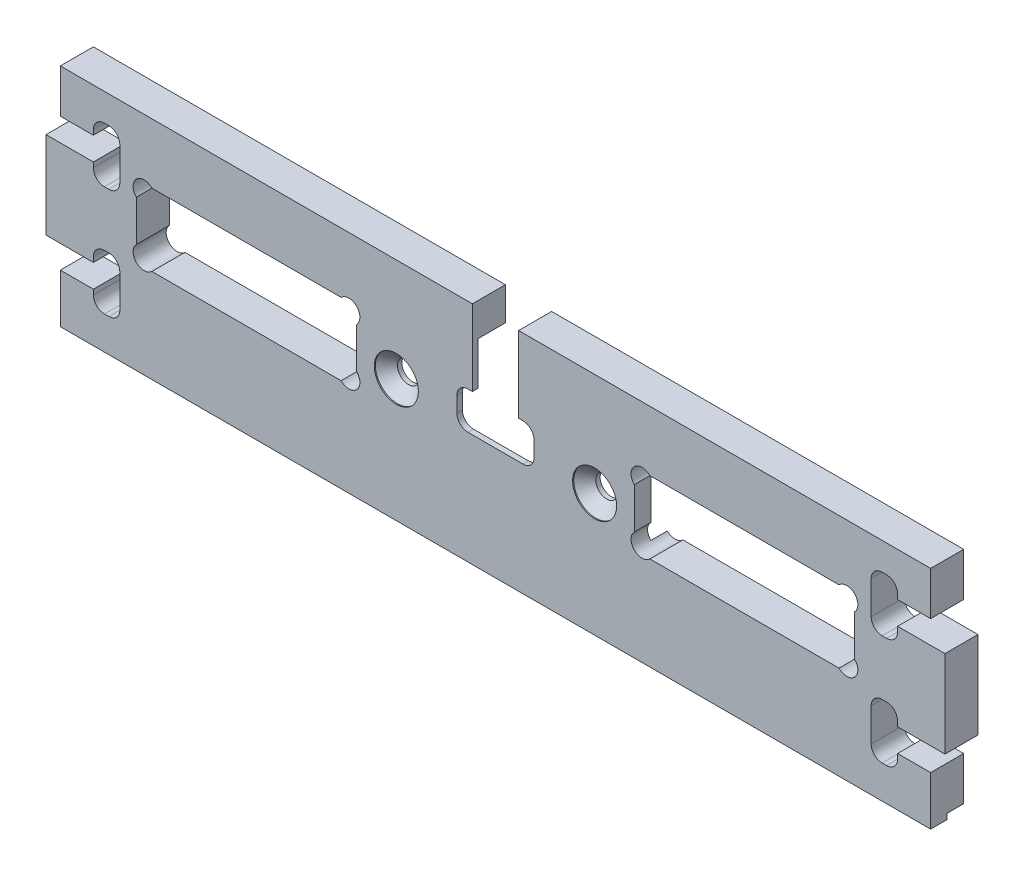
SolidWorks part; units mm, degrees
ref_plane "Front Plane" through (0, 0, 0) normal (0, 0, 1) x (1, 0, 0)
ref_plane "Top Plane" through (0, 0, 0) normal (0, 1, 0) x (1, 0, 0)
ref_plane "Right Plane" through (0, 0, 0) normal (1, 0, 0) x (0, 0, -1)
sketch "Sketch1" plane through (0, 0, 0) normal (0, 0, 1) x (1, 0, 0)
  line L0 (-39.5, 0) -> (39.5, 0) construction
  line L1 (-39.5, 10) -> (39.5, 10)
  line L2 (-39.5, 10) -> (-39.5, -10)
  line L3 (-39.5, -10) -> (39.5, -10)
  line L4 (39.5, 10) -> (39.5, -10)
  line L5 (-39.5, 10) -> (39.5, -10) construction
  line L6 (-39.5, -10) -> (39.5, 10) construction
  line L7 (0, 10) -> (0, -10) construction
  line L9 (-40.8, -3.95) -> (-39.5, -3.95)
  line L10 (-40.8, -3.95) -> (-40.8, 3.95)
  line L11 (-40.8, 3.95) -> (-39.5, 3.95)
  line L12 (-39.5, -3.95) -> (-39.5, 3.95)
  line L13 (-40.8, -3.95) -> (-39.5, 3.95) construction
  line L14 (-40.8, 3.95) -> (-39.5, -3.95) construction
  line L16 (40.8, 3.95) -> (39.5, 3.95)
  line L17 (40.8, -3.95) -> (40.8, 3.95)
  line L18 (40.8, -3.95) -> (39.5, -3.95)
  line L19 (-39.5, 5) -> (39.5, 5) construction
  line L20 (-35.3, 7.5) -> (-35.3, 2.5) construction
  line L21 (-36.5, 3.95) -> (-39.5, 3.95)
  line L22 (-36.5, 3.95) -> (-36.5, 6.05)
  line L23 (-36.5, 6.05) -> (-39.5, 6.05)
  line L24 (-39.5, 3.95) -> (-39.5, 6.05)
  line L25 (-36.5, 3.95) -> (-39.5, 6.05) construction
  line L26 (-36.5, 6.05) -> (-39.5, 3.95) construction
  line L27 (-34.1, 7.5) -> (-36.5, 7.5)
  line L28 (-34.1, 7.5) -> (-34.1, 2.5)
  line L29 (-34.1, 2.5) -> (-36.5, 2.5)
  line L30 (-36.5, 7.5) -> (-36.5, 2.5)
  line L31 (-34.1, 7.5) -> (-36.5, 2.5) construction
  line L32 (-34.1, 2.5) -> (-36.5, 7.5) construction
  line L33 (-34.1, -7.5) -> (-36.5, -7.5)
  line L34 (-34.1, -7.5) -> (-34.1, -2.5)
  line L35 (-34.1, -2.5) -> (-36.5, -2.5)
  line L36 (-36.5, -7.5) -> (-36.5, -2.5)
  line L37 (-36.5, -3.95) -> (-39.5, -3.95)
  line L38 (-36.5, -6.05) -> (-39.5, -6.05)
  line L39 (36.5, 3.95) -> (39.5, 3.95)
  line L40 (36.5, 6.05) -> (39.5, 6.05)
  line L41 (36.5, 7.5) -> (36.5, 2.5)
  line L42 (34.1, 7.5) -> (36.5, 7.5)
  line L43 (34.1, 7.5) -> (34.1, 2.5)
  line L44 (34.1, 2.5) -> (36.5, 2.5)
  line L45 (34.1, -2.5) -> (36.5, -2.5)
  line L46 (34.1, -7.5) -> (34.1, -2.5)
  line L47 (34.1, -7.5) -> (36.5, -7.5)
  line L48 (36.5, -7.5) -> (36.5, -2.5)
  line L49 (36.5, -6.05) -> (39.5, -6.05)
  line L50 (36.5, -3.95) -> (39.5, -3.95)
  point P0 (0, 0)
  point P10 (-40.15, 0)
  point P15 (-38, 5)
  point P35 (-35.3, 5)
  dimension "D1" = 79
  dimension "D2" = 20
  dimension "D4" = 1.3
  dimension "D7" = 5
  dimension "D8" = 2.1
  dimension "D9" = 3
  dimension "D10" = 2.4
  dimension "D11" = 5
extrude "Base shape" add sketch "Sketch1" along normal blind 3 contours L4 L1 L2 L3 | L9 L2 L11 L10 | L16 L4 L18 L17 region at (0, 0, 0) region at (-40.15, 0, 0) region at (40.15, 0, 0)
sketch "Sketch4" plane through (0, -10, 0) normal (0, -1, 0) x (1, 0, 0)
  line L0 (39.5, 3) -> (39.5, 0) construction
  line L1 (-39.5, 3) -> (39.5, 3)
  line L2 (-39.5, 3) -> (-39.5, 1.5)
  line L3 (-39.5, 1.5) -> (39.5, 1.5)
  line L4 (39.5, 3) -> (39.5, 1.5)
extrude "Floor lip" add sketch "Sketch4" along normal blind 0.5
sketch "Sketch6" plane through (0, 0, 0) normal (0, 0, -1) x (-1, 0, 0)
  line L0 (0, 0) -> (0, -10) construction
  line L1 (39.5, -10) -> (-39.5, -10) construction
  line L2 (-4, -10) -> (4, -10) construction
  line L3 (39.5, -10) -> (-39.5, -10) construction
  line L4 (-4, -9) -> (4, -9)
  line L5 (-4, -11) -> (4, -11)
  arc A0 (-4, -9) -> (-4, -11) centre (-4, -10) ccw
  arc A1 (4, -11) -> (4, -9) centre (4, -10) ccw
  point P9 (0, -10)
  dimension "D1" = 2
  dimension "D2" = 8
extrude "Nail cutout" cut sketch "Sketch6" against normal up to surface (1.5 mm away) up to face at (0, -10.25, 1.5)
sketch "Sketch3" plane through (-40.8, 0, 0) normal (-1, 0, 0) x (0, 0, 1)
  line L0 (0, 6.05) -> (3, 3.95) construction
  line L1 (0, 6.05) -> (3, 6.05)
  line L2 (0, 6.05) -> (0, 3.95)
  line L3 (0, 3.95) -> (3, 3.95)
  line L4 (3, 6.05) -> (3, 3.95)
  line L5 (0, -3.95) -> (3, -6.05) construction
  line L6 (0, -3.95) -> (3, -3.95)
  line L7 (0, -3.95) -> (0, -6.05)
  line L8 (0, -6.05) -> (3, -6.05)
  line L9 (3, -3.95) -> (3, -6.05)
  point P6 (1.5, 5)
  point P13 (1.5, -5)
ref_axis "Tap axis top" through (-53.7846, 5, 1.5) along (1, 0, 0)
ref_axis "Tap axis bottom" through (-54.2844, -5, 1.5) along (1, 0, 0)
fillet "Mill fillets" radius 1 16 edges at (36.5, -7.5, 1.5) (36.5, 2.5, 1.5) (34.1, 2.5, 1.5) (34.1, -7.5, 1.5) (36.5, -2.5, 1.5) (36.5, 7.5, 1.5) (34.1, -2.5, 1.5) (34.1, 7.5, 1.5) (-36.5, -2.5, 1.5) (-34.1, -2.5, 1.5) (-34.1, -7.5, 1.5) (-36.5, -7.5, 1.5) (-36.5, 2.5, 1.5) (-34.1, 2.5, 1.5) (-34.1, 7.5, 1.5) (-36.5, 7.5, 1.5)
sketch "Sketch8" [suppressed] plane through (0, 0, 3) normal (0, 0, 1) x (1, 0, 0)
  line L0 (-40.8, 0) -> (40.8, 0) construction
  line L1 (-40.8, -3.95) -> (-40.8, 3.95) construction
  line L2 (40.8, -3.95) -> (40.8, 3.95) construction
  line L4 (-24.5, 5.15) -> (24.5, 5.15)
  line L5 (-25.5, 4.15) -> (-25.5, -4.15)
  line L6 (-24.5, -5.15) -> (24.5, -5.15)
  line L7 (25.5, 4.15) -> (25.5, -4.15)
  line L8 (-25.5, 5.15) -> (25.5, -5.15) construction
  line L9 (-25.5, -5.15) -> (25.5, 5.15) construction
  arc A0 (24.5, -5.15) -> (25.5, -4.15) centre (24.5, -4.15) ccw
  arc A1 (24.5, 5.15) -> (25.5, 4.15) centre (24.5, 4.15) cw
  arc A2 (-25.5, -4.15) -> (-24.5, -5.15) centre (-24.5, -4.15) ccw
  arc A3 (-24.5, 5.15) -> (-25.5, 4.15) centre (-24.5, 4.15) ccw
  point P6 (0, 0)
  dimension "D3" = 1
  dimension "D1" = 51
  dimension "D2" = 10.3
extrude "Led strip pocket" [suppressed] cut sketch "Sketch8" against normal offset from surface (2.5 mm away) 0.5 up to face at (0, -0.6712, 0)
sketch "Sketch9" [suppressed] plane through (0, 0, 0.5) normal (0, 0, 1) x (1, 0, 0)
  line L0 (-19.5, 5.15) -> (-19.5, -5.15)
  line L1 (0, 5.15) -> (0, -5.15) construction
  line L2 (19.5, 5.15) -> (19.5, -5.15)
  line L3 (-25.5, -2.978) -> (25.5, -2.978) construction
  line L4 (25.5, -4.15) -> (25.5, 4.15)
  line L5 (24.5, 5.15) -> (-24.5, 5.15)
  line L6 (-25.5, 4.15) -> (-25.5, -4.15)
  line L7 (-24.5, -5.15) -> (24.5, -5.15)
  line L8 (25.5, -4.15) -> (25.5, 4.15)
  line L9 (24.5, 5.15) -> (-24.5, 5.15)
  line L10 (-25.5, 4.15) -> (-25.5, -4.15)
  line L11 (-24.5, -5.15) -> (24.5, -5.15)
  circle A0 centre (-12.7, -2.978) radius 1
  circle A1 centre (12.7, -2.978) radius 1
  arc A4 (24.5, -5.15) -> (25.5, -4.15) centre (24.5, -4.15) ccw
  arc A5 (25.5, 4.15) -> (24.5, 5.15) centre (24.5, 4.15) ccw
  arc A6 (-24.5, 5.15) -> (-25.5, 4.15) centre (-24.5, 4.15) ccw
  arc A7 (-25.5, -4.15) -> (-24.5, -5.15) centre (-24.5, -4.15) ccw
  arc A8 (24.5, -5.15) -> (25.5, -4.15) centre (24.5, -4.15) ccw
  arc A9 (25.5, 4.15) -> (24.5, 5.15) centre (24.5, 4.15) ccw
  arc A10 (-24.5, 5.15) -> (-25.5, 4.15) centre (-24.5, 4.15) ccw
  arc A11 (-25.5, -4.15) -> (-24.5, -5.15) centre (-24.5, -4.15) ccw
  arc M13 (24.5, -5.15) -> (25.5, -4.15) centre (24.5, -4.15) ccw
  line M14 (25.5, -4.15) -> (25.5, 4.15)
  arc M15 (25.5, 4.15) -> (24.5, 5.15) centre (24.5, 4.15) ccw
  line M16 (24.5, 5.15) -> (-24.5, 5.15)
  arc M17 (-24.5, 5.15) -> (-25.5, 4.15) centre (-24.5, 4.15) ccw
  line M18 (-25.5, 4.15) -> (-25.5, -4.15)
  arc M19 (-25.5, -4.15) -> (-24.5, -5.15) centre (-24.5, -4.15) ccw
  line M20 (-24.5, -5.15) -> (24.5, -5.15)
  dimension "D4" = 2
  dimension "D2" = 6
  dimension "D3" = 8.128
  dimension "D5" = 25.4
  dimension "D1" = 0
extrude "Led strip cuts" [suppressed] cut sketch "Sketch9" against normal up to next contours L0 M16 M17 M18 M19 M20 | L2 M16 M20 M13 M14 M15 | A0 | A1
fillet "Led strip cut fillets" [suppressed] radius 1
sketch "Sketch13" plane through (0, 0, 0) normal (0, 0, -1) x (-1, 0, 0)
  line L0 (0, 15.8648) -> (0, -21.9195) construction
  line L2 (-4.1, -5.7) -> (4.1, -5.7)
  line L3 (-5.1, -4.7) -> (-5.1, 6)
  line L4 (-4.1, 7) -> (4.1, 7)
  line L5 (5.1, -4.7) -> (5.1, 6)
  line L6 (-5.1, -5.7) -> (5.1, 7) construction
  line L7 (-5.1, 7) -> (5.1, -5.7) construction
  line L10 (39.5, 10) -> (-39.5, 10) construction
  arc A0 (-4.1, -5.7) -> (-5.1, -4.7) centre (-4.1, -4.7) cw
  arc A1 (4.1, -5.7) -> (5.1, -4.7) centre (4.1, -4.7) ccw
  arc A4 (5.1, 6) -> (4.1, 7) centre (4.1, 6) ccw
  arc A5 (-5.1, 6) -> (-4.1, 7) centre (-4.1, 6) cw
  point P1 (0, 0.65)
  point P8 (0, 0)
  point P9 (5.5684, 9.0125)
  point P16 (0, 0)
  point P17 (0, 0)
  dimension "D4" = 1
  dimension "D5" = 1
  dimension "D1" = 10.2
  dimension "D2" = 12.7
  dimension "D3" = 3
extrude "Bumper mount inner cut" cut sketch "Sketch13" against normal offset from surface (2.5 mm away) 0.5 up to face at (0, -0.0192, 3)
sketch "Sketch14" plane through (0, 0, 0) normal (0, 0, -1) x (-1, 0, 0)
  line L1 (0, 12.9528) -> (0, -14.0841) construction
  line L2 (4.1, 7) -> (-4.1, 7) construction
  line L3 (-4.1, -5.7) -> (4.1, -5.7) construction
  line L4 (-11.6, 7) -> (11.6, 7)
  line L5 (-12.6, 6) -> (-12.6, -4.7)
  line L6 (-11.6, -5.7) -> (11.6, -5.7)
  line L7 (12.6, 6) -> (12.6, -4.7)
  line L8 (-12.6, 7) -> (12.6, -5.7) construction
  line L9 (-12.6, -5.7) -> (12.6, 7) construction
  arc A1 (11.6, -5.7) -> (12.6, -4.7) centre (11.6, -4.7) ccw
  arc A2 (-12.6, -4.7) -> (-11.6, -5.7) centre (-11.6, -4.7) ccw
  arc A3 (11.6, 7) -> (12.6, 6) centre (11.6, 6) cw
  arc A4 (-12.6, 6) -> (-11.6, 7) centre (-11.6, 6) cw
  point P6 (0, 0.65)
  dimension "D2" = 1
  dimension "D3" = 1
  dimension "D1" = 25.2
extrude "Bumper mount outer cut" cut sketch "Sketch14" against normal blind 1.5
sketch "Sketch15" plane through (0, 0, 1.5) normal (0, 0, -1) x (-1, 0, 0)
  line L0 (-12.6, 0.65) -> (12.6, 0.65) construction
  line L3 (0, 16.4744) -> (0, -20.0474) construction
  line L4 (11.6, 7) -> (11.6, -5.7) construction
  line L6 (-11.6, -5.7) -> (11.6, -5.7) construction
  line L7 (-12.6, 6) -> (-12.6, -4.7) construction
  line L8 (12.6, -4.7) -> (12.6, 6) construction
  line L9 (11.6, 7) -> (4.1, 7) construction
  circle A0 centre (-9, 0.65) radius 1
  circle A1 centre (9, 0.65) radius 1
  point P2 (11.6, 0.65)
  point P5 (10, 7)
  point P13 (0, 0)
  point P19 (0, 0)
  point P22 (0, 0)
  point P24 (0, 0)
  point P25 (8.6174, -5.7)
  point P26 (0, 0)
  point P29 (0, 0)
  point P30 (13.4221, 7)
  dimension "D1" = 18
  dimension "D2" = 2
extrude "Bumper mount screw holes" cut sketch "Sketch15" against normal up to next
sketch "Sketch16" plane through (0, 0, 2.5) normal (0, 0, -1) x (-1, 0, 0)
  line L0 (-5.1, 1.4) -> (5.1, 1.4) construction
  line L3 (0, 7) -> (0, -4.2) construction
  line L4 (-2.5, 3.1) -> (2.5, 3.1)
  line L5 (-3.5, 2.1) -> (-3.5, 0.7)
  line L6 (-2.5, -0.3) -> (2.5, -0.3)
  line L7 (3.5, 2.1) -> (3.5, 0.7)
  line L8 (-3.5, 3.1) -> (3.5, -0.3) construction
  line L9 (-3.5, -0.3) -> (3.5, 3.1) construction
  line L11 (-5.1, 6) -> (-5.1, -4.7) construction
  line L13 (4.1, 7) -> (-4.1, 7) construction
  arc A0 (2.5, -0.3) -> (3.5, 0.7) centre (2.5, 0.7) ccw
  arc A1 (-3.5, 0.7) -> (-2.5, -0.3) centre (-2.5, 0.7) ccw
  arc A2 (-2.5, 3.1) -> (-3.5, 2.1) centre (-2.5, 2.1) ccw
  arc A3 (2.5, 3.1) -> (3.5, 2.1) centre (2.5, 2.1) cw
  point P2 (0, 0)
  point P5 (0, 0)
  point P6 (0, 1.4)
  point P23 (0, 0)
  point P24 (0, 7.9459)
  point P29 (0, 0)
  dimension "D3" = 1
  dimension "D1" = 7
  dimension "D2" = 3.4
  dimension "D4" = 11.2
extrude "Bumper body cut" cut sketch "Sketch16" against normal up to next
hole_wizard "Bumper screw countersunks" positions "Sketch17" profile "Sketch18" countersink size "M2" standard "ANSI Metric" end condition through all
sketch "Sketch17" plane through (0, 0, 3) normal (0, 0, 1) x (1, 0, 0)
  point P0 (9, 0.65)
  point P3 (-9, 0.65)
sketch "Sketch18" plane through (9, 0.65, 3) normal (1, 0, 0) x (0, -1, 0)
  line L0 (0, 0) -> (0, 3)
  line L1 (0, 3) -> (1, 3)
  line L2 (1, 3) -> (1, 1.1)
  line L3 (1, 1.1) -> (2, 0.1)
  line L4 (2, 0.1) -> (2, 0)
  line L6 (2, 0) -> (0, 0)
  line L7 (-1, 1.1) -> (-2, 0.1) construction
  line L11 (0, -6.35) -> (0, 107.95) construction
  dimension "Thru Hole Dia." = 2
  dimension "Thru Hole Depth" = 3
  dimension "C'Sink Dia." = 4
  dimension "C'Sink Angle" = 90
  dimension "Head Clearance" = 0.1
sketch "Sketch19" plane through (0, 0, 0) normal (0, 0, -1) x (-1, 0, 0)
  line L0 (0, 15.6498) -> (0, -12.9575) construction
  line L1 (39.5, 10) -> (-39.5, 10) construction
  line L2 (-2.1, 3.1) -> (2.1, 3.1)
  line L3 (-2.1, 3.1) -> (-2.1, 10)
  line L4 (-2.1, 10) -> (2.1, 10)
  line L5 (2.1, 3.1) -> (2.1, 10)
  line L6 (-2.1, 3.1) -> (2.1, 10) construction
  line L7 (-2.1, 10) -> (2.1, 3.1) construction
  line L8 (2.5, 3.1) -> (-2.5, 3.1) construction
  point P1 (0, 6.55)
  dimension "D1" = 4.2
extrude "Bumper insertion cut" cut sketch "Sketch19" against normal up to next
sketch "Sketch20" plane through (0, 0, 0) normal (0, 0, -1) x (-1, 0, 0)
  line L0 (-12.6, 6) -> (-12.6, -4.7) construction
  line L1 (-12.6, 4.55) -> (-32.6, 4.55)
  line L2 (-12.6, 4.55) -> (-12.6, -2)
  line L3 (-12.6, -2) -> (-32.6, -2)
  line L4 (-32.6, 4.55) -> (-32.6, -2)
  line L5 (-2.1, 10) -> (-39.5, 10) construction
  line L6 (-12.6, 4.55) -> (-19.15, -2) construction
  line L7 (-22.6, 4.55) -> (-22.6, -2) construction
  line L8 (-32.6, 1.275) -> (-12.6, 1.275) construction
  line L9 (0, 16.176) -> (0, -15.99) construction
  line L10 (12.6, 4.55) -> (12.6, -2)
  line L11 (12.6, -2) -> (32.6, -2)
  line L12 (32.6, 4.55) -> (32.6, -2)
  line L13 (12.6, 4.55) -> (32.6, 4.55)
  circle A0 centre (-13.3071, 3.8429) radius 1
  circle A1 centre (-31.8929, 3.8429) radius 1
  circle A2 centre (-13.3071, -1.2929) radius 1
  circle A3 centre (-31.8929, -1.2929) radius 1
  circle A4 centre (13.3071, 3.8429) radius 1
  circle A5 centre (13.3071, -1.2929) radius 1
  circle A6 centre (31.8929, -1.2929) radius 1
  circle A7 centre (31.8929, 3.8429) radius 1
  dimension "D5" = 2
  dimension "D1" = 20
  dimension "D2" = 5.45
  dimension "D3" = 6.55
  dimension "D4" = 45
extrude "Cut-Extrude2" cut sketch "Sketch20" against normal up to next contours L1 L4 L3 L2 | A1 | A3 | A0 | A2 | L13 L12 L11 L10 | A4 | A5 | A6 | A7
